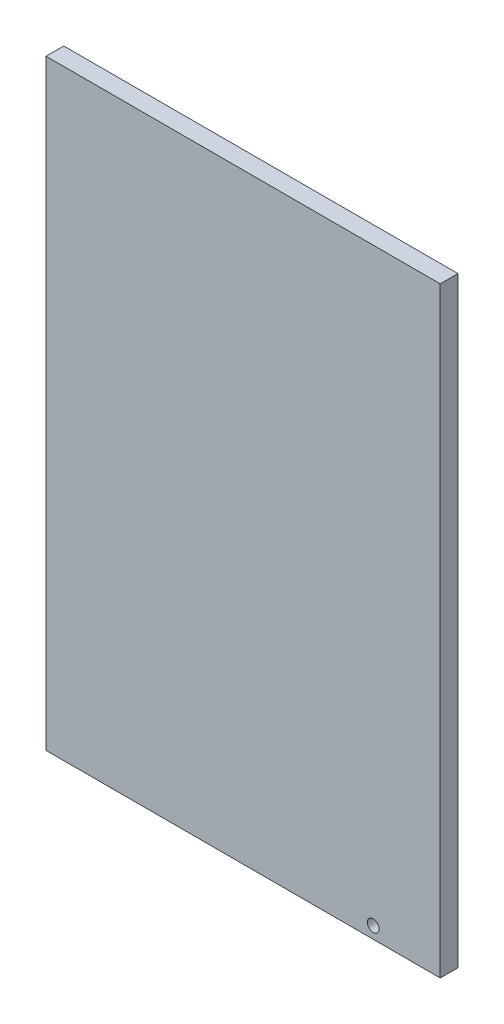
SolidWorks part; units mm, degrees
ref_plane "Front Plane" through (0, 0, 0) normal (0, 0, 1) x (1, 0, 0)
ref_plane "Top Plane" through (0, 0, 0) normal (0, 1, 0) x (1, 0, 0)
ref_plane "Right Plane" through (0, 0, 0) normal (1, 0, 0) x (0, 0, -1)
sketch "Sketch1" plane through (0, 0, 0) normal (0, 0, 1) x (1, 0, 0)
  line L1 (-100, -152.5) -> (100, -152.5)
  line L2 (-100, -152.5) -> (-100, 152.5)
  line L3 (-100, 152.5) -> (100, 152.5)
  line L4 (100, -152.5) -> (100, 152.5)
  line L5 (-100, -152.5) -> (100, 152.5) construction
  line L6 (-100, 152.5) -> (100, -152.5) construction
  point P0 (0, 0)
  dimension "D1" = 200
  dimension "D2" = 305
extrude "Boss-Extrude1" add sketch "Sketch1" along normal blind 9
sketch "Sketch2" plane through (0, 0, 9) normal (0, 0, 1) x (1, 0, 0)
  line L0 (100, -152.5) -> (100, 152.5) construction
  line L1 (-100, -152.5) -> (100, -152.5) construction
  circle A0 centre (66, -146.5) radius 3
  dimension "D1" = 6
  dimension "D2" = 34
  dimension "D3" = 6
extrude "Cut-Extrude1" cut sketch "Sketch2" against normal through all
sketch "Sketch3" [suppressed] plane through (0, 0, 0) normal (0, 0, -1) x (-1, 0, 0)
  line L0 (-120.2594, -152.5) -> (119.7406, -152.5) construction
  line L2 (-90.2594, -139.5) -> (-30.2594, -139.5) construction
  line L3 (-30.2594, -139.5) -> (29.7406, -139.5) construction
  line L4 (29.7406, -139.5) -> (89.7406, -139.5) construction
  circle A0 centre (-90.2594, -139.5) radius 4.75
  circle A1 centre (-30.2594, -139.5) radius 5.5875
  circle A2 centre (29.7406, -139.5) radius 4.75
  circle A3 centre (89.7406, -139.5) radius 5.5875
  point P3 (-0.2594, -152.5)
  dimension "D2" = 9.5
  dimension "D7" = 11.175
  dimension "D1" = 240
  dimension "D3" = 13
  dimension "D4" = 30
  dimension "D5" = 60
  dimension "D6" = 60
  dimension "60" = 60
extrude "Cut-Extrude2" [suppressed] cut sketch "Sketch3" against normal through all
equation "\"PCLength\"= 320mm'Length across I/O from PS to GPU"
equation "\"PCWidth\"= 242mm'Distance of longest part parallel to GPU(ussually GPU)"
equation "\"PCHeight\"= 172mm'Tallest point with mobo laying flat"
equation "\"WallThickness\"= 9mm'Thickness of each outer tank wall"
equation "\"ThermoBarrierThickness\"= 3mm'Thickness of barrier between hot side and cold side"
equation "\"HotSideGap\"= 25mm'Space in the hot side for a pump"
equation "\"PCClearance\"= 30mm'Clearance from top of tank to top of PC"
equation "\"RadiatorHeight\"= 275mm'Final Height from ground of radiators"
equation "\"D1@Sketch1\"=\"PCHeight\" + \"ThermoBarrierThickness\" + \"HotSideGap\""
equation "\"D2@Sketch1\"=\"RadiatorHeight\" + \"PCClearance\""
equation "\"D1@Boss-Extrude1\"=\"WallThickness\""
equation "\"D2@Sketch2\"=\"HotSideGap\" + \"ThermoBarrierThickness\" + 6"
